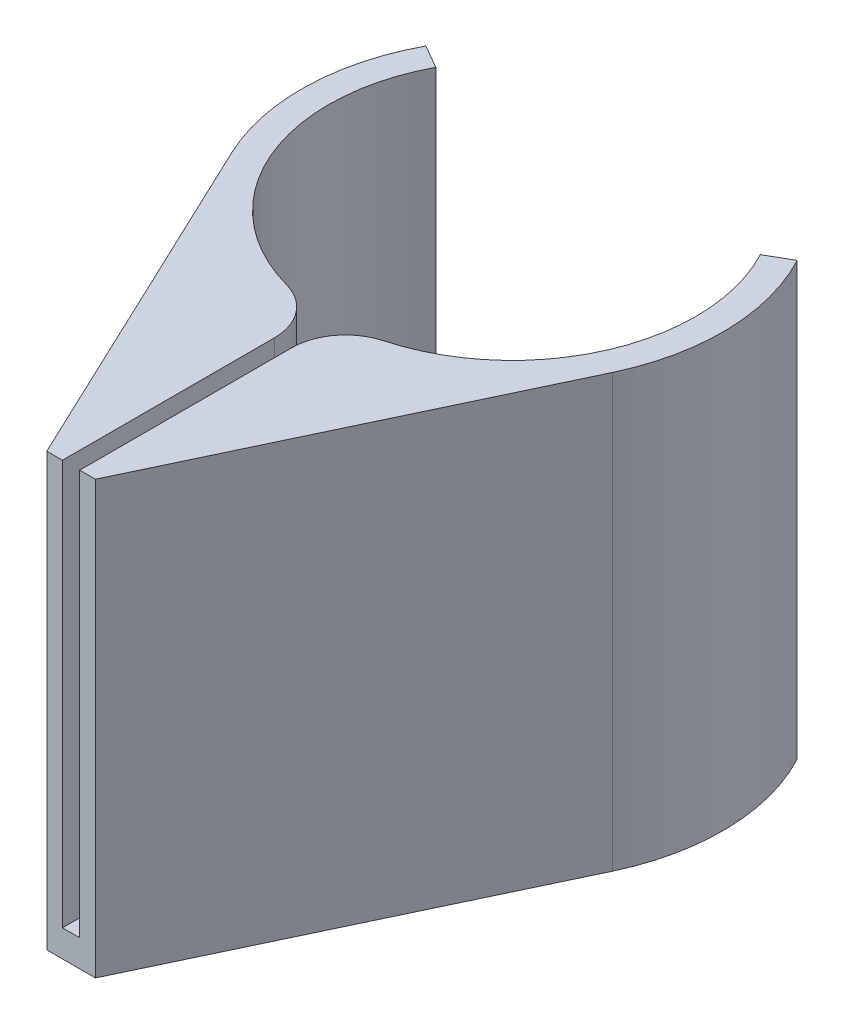
SolidWorks part; units mm, degrees
ref_plane "Front Plane" through (0, 0, 0) normal (0, 0, 1) x (1, 0, 0)
ref_plane "Top Plane" through (0, 0, 0) normal (0, 1, 0) x (1, 0, 0)
ref_plane "Right Plane" through (0, 0, 0) normal (1, 0, 0) x (0, 0, -1)
sketch "body tube profile" plane through (0, 0, 0) normal (0, 1, 0) x (1, 0, 0)
  circle A0 centre (0, 0) radius 34
  dimension "D1" = 68
sketch "Sketch2" plane through (0, 0, 0) normal (0, 1, 0) x (1, 0, 0)
  line L1 (0, 0) -> (0, -34) construction
  line L2 (-35.2539, -16.6782) -> (-4.5, -81.685)
  line L13 (29.4449, 17) -> (33.775, 19.5) construction
  line L14 (-4.5, -81.685) -> (4.5, -81.685)
  line L15 (30.05, 15.906) -> (34.3826, 18.4074)
  line L16 (0, -55) -> (0, 55) construction
  line L17 (-30.05, 15.906) -> (-34.3826, 18.4074)
  line L18 (4.5, -81.685) -> (35.2539, -16.6782)
  circle A0 centre (0, 0) radius 39 construction
  circle A3 centre (0, 0) radius 34 construction
  arc A4 (-30.05, 15.906) -> (30.05, 15.906) centre (0, 0) ccw
  arc A6 (-34.3826, 18.4074) -> (-35.2539, -16.6782) centre (0, 0) ccw
  circle A7 centre (0, 0) radius 34 construction
  arc A8 (35.2539, -16.6782) -> (34.3826, 18.4074) centre (0, 0) ccw
  point P10 (0, -81.685)
  dimension "D2" = 9
  dimension "D3" = 120
  dimension "D4" = 81.685
  dimension "D5" = 2.5
  dimension "D6" = 5
  dimension "D1" = 5
extrude "Fin slot extrude" add sketch "Sketch2" along normal blind 80 contours L17 region at (0, 0, 39.8733)
sketch "Sketch3" plane through (0, 80, 0) normal (0, 1, 0) x (1, 0, 0)
  line L0 (0, -81.685) -> (0, -34) construction
  line L1 (-4.5, -81.685) -> (4.5, -81.685) construction
  line L2 (1.6, -81.685) -> (1.6, -33.9623)
  line L3 (-1.6, -81.685) -> (-1.6, -33.9623)
  line L4 (-1.6, -81.685) -> (1.6, -81.685)
  arc A0 (-30.05, 15.906) -> (30.05, 15.906) centre (0, 0) ccw construction
  arc A1 (-1.6, -33.9623) -> (1.6, -33.9623) centre (0, 0) ccw
  dimension "D1" = 1.6
extrude "Fin slot" cut sketch "Sketch3" against normal offset from surface (75 mm away) 5 up to face at (0, 0, 22.2248)
fillet "Fillet1" radius 10 3 edges at (0, 5, 34) (1.6, 42.5, 33.9623) (-1.6, 42.5, 33.9623)
